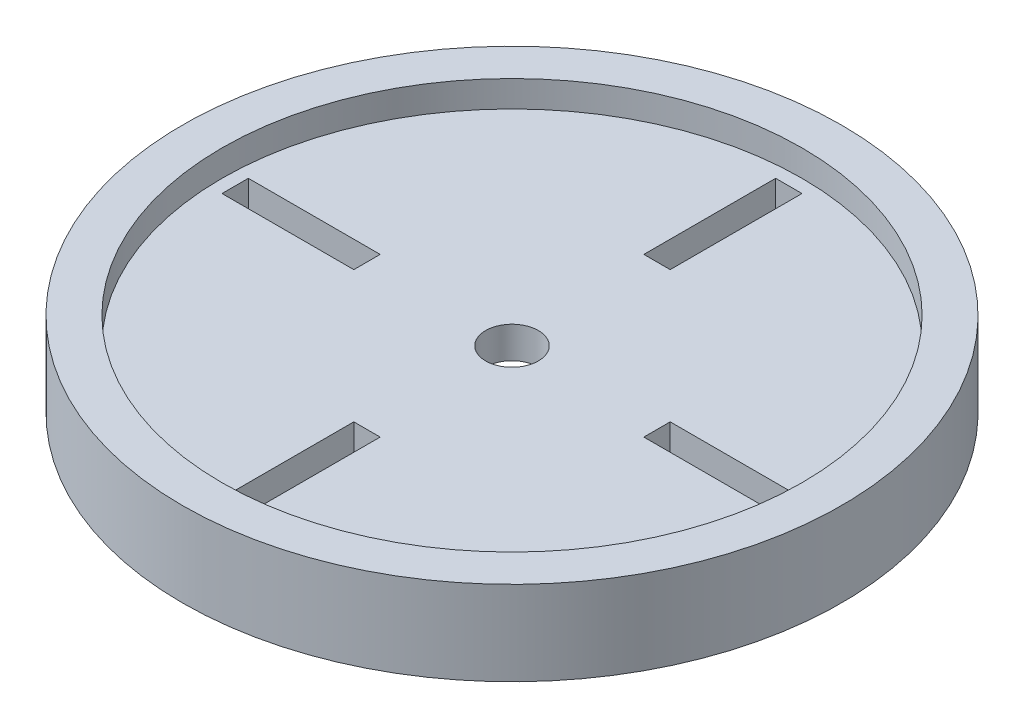
SolidWorks part; units mm, degrees
ref_plane "Front Plane" through (0, 0, 0) normal (0, 0, 1) x (1, 0, 0)
ref_plane "Top Plane" through (0, 0, 0) normal (0, 1, 0) x (1, 0, 0)
ref_plane "Right Plane" through (0, 0, 0) normal (1, 0, 0) x (0, 0, -1)
sketch "Sketch1" plane through (0, 0, 0) normal (0, 1, 0) x (1, 0, 0)
  circle A0 centre (0, 0) radius 62.5
  dimension "D1" = 125
extrude "Boss-Extrude1" add sketch "Sketch1" along normal blind 8 and the other way blind 8
sketch "Sketch2" plane through (0, 8, 0) normal (0, 1, 0) x (1, 0, 0)
  circle A0 centre (0, 0) radius 55
  dimension "D1" = 110
extrude "Cut-Extrude1" cut sketch "Sketch2" against normal blind 5
sketch "Sketch3" plane through (0, -8, 0) normal (0, -1, 0) x (1, 0, 0)
  circle A0 centre (0, 0) radius 55
  dimension "D1" = 110
extrude "Cut-Extrude2" cut sketch "Sketch3" against normal blind 5
sketch "Sketch4" plane through (0, -3, 0) normal (0, -1, 0) x (1, 0, 0)
  circle A0 centre (0, 0) radius 5
  dimension "D1" = 10
extrude "Cut-Extrude3" cut sketch "Sketch4" against normal through all
sketch "Sketch5" plane through (0, -3, 0) normal (0, -1, 0) x (1, 0, 0)
  line L1 (2.5, 27.5) -> (-2.5, 27.5)
  line L2 (2.5, 27.5) -> (2.5, 52.5)
  line L3 (2.5, 52.5) -> (-2.5, 52.5)
  line L4 (-2.5, 27.5) -> (-2.5, 52.5)
  line L5 (2.5, 27.5) -> (-2.5, 52.5) construction
  line L6 (2.5, 52.5) -> (-2.5, 27.5) construction
  point P0 (0, 40)
  point P5 (0, 0)
  point P7 (-7.3157, 24.3379)
  point P9 (0, 0)
  dimension "D1" = 25
  dimension "D2" = 5
  dimension "D3" = 40
extrude "Cut-Extrude4" cut sketch "Sketch5" against normal through all
pattern_circular "CirPattern1" count 4 over 360 about axis through (0, -8, 0) along (0, 1, 0) of "Cut-Extrude4" reverse direction yes
